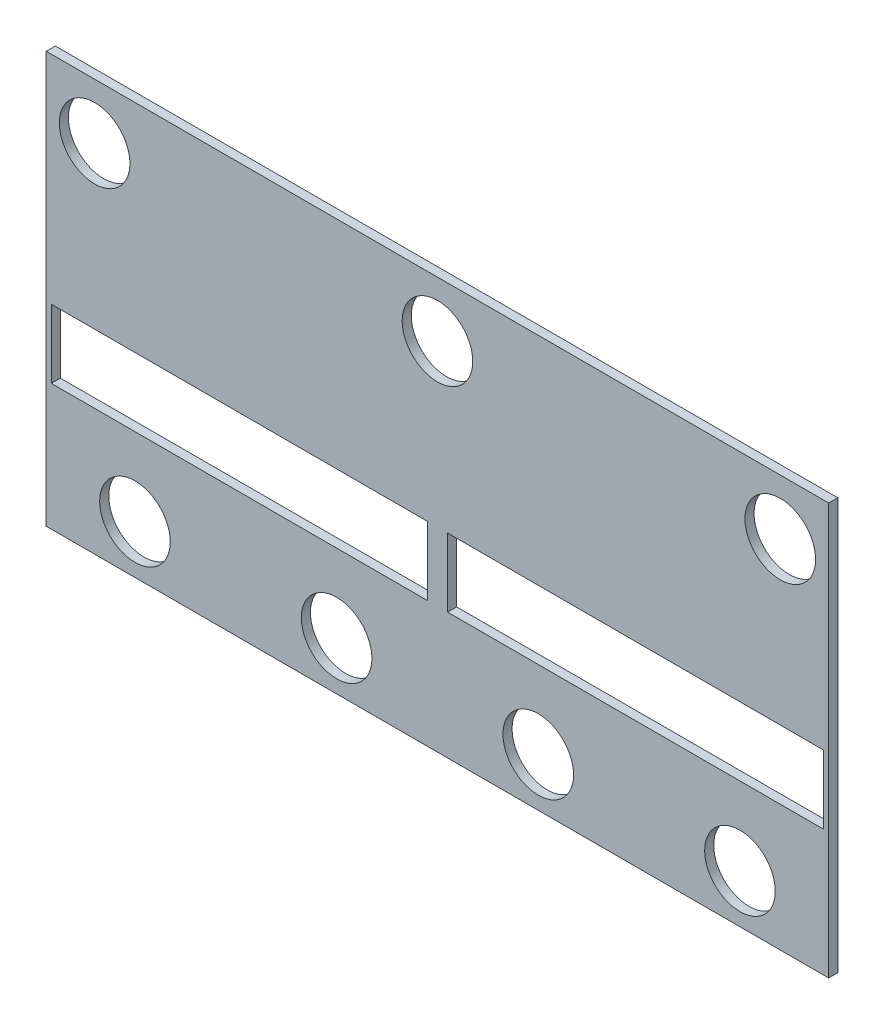
SolidWorks part; units mm, degrees
material "PLA"
ref_plane "Front" through (0, 0, 0) normal (0, 0, 1) x (1, 0, 0)
ref_plane "Top" through (0, 0, 0) normal (0, 1, 0) x (1, 0, 0)
ref_plane "Right" through (0, 0, 0) normal (1, 0, 0) x (0, 0, -1)
sketch "Sketch14" plane through (0, 0, 0) normal (0, 0, 1) x (1, 0, 0)
  line L0 (8.575, 1.875) -> (8.575, -1.875)
  line L1 (2.275, 1.875) -> (6.025, 1.875)
  line L2 (2.275, 1.875) -> (2.275, -1.875)
  line L3 (2.275, -1.875) -> (6.025, -1.875)
  line L4 (6.025, 1.875) -> (6.025, -1.875)
  line L5 (8.575, 1.875) -> (12.325, 1.875)
  line L6 (12.325, 1.875) -> (12.325, -1.875)
  line L7 (8.575, -1.875) -> (12.325, -1.875)
  line L8 (14.875, 1.875) -> (14.875, -1.875)
  line L9 (14.875, 1.875) -> (18.625, 1.875)
  line L10 (18.625, 1.875) -> (18.625, -1.875)
  line L11 (14.875, -1.875) -> (18.625, -1.875)
  line L12 (21.175, 1.875) -> (21.175, -1.875)
  line L13 (21.175, 1.875) -> (24.925, 1.875)
  line L14 (24.925, 1.875) -> (24.925, -1.875)
  line L15 (21.175, -1.875) -> (24.925, -1.875)
  line L16 (27.475, 1.875) -> (27.475, -1.875)
  line L17 (27.475, 1.875) -> (31.225, 1.875)
  line L18 (31.225, 1.875) -> (31.225, -1.875)
  line L19 (27.475, -1.875) -> (31.225, -1.875)
  line L20 (33.775, 1.875) -> (33.775, -1.875)
  line L21 (33.775, 1.875) -> (37.525, 1.875)
  line L22 (37.525, 1.875) -> (37.525, -1.875)
  line L23 (33.775, -1.875) -> (37.525, -1.875)
  line L24 (2.275, 1.875) -> (8.575, 1.875) construction
  line L25 (0, 1.875) -> (0, -1.875) construction
  line L26 (-33.775, -1.875) -> (-37.525, -1.875)
  line L27 (-37.525, 1.875) -> (-37.525, -1.875)
  line L28 (-33.775, 1.875) -> (-37.525, 1.875)
  line L29 (-33.775, 1.875) -> (-33.775, -1.875)
  line L30 (-27.475, -1.875) -> (-31.225, -1.875)
  line L31 (-31.225, 1.875) -> (-31.225, -1.875)
  line L32 (-27.475, 1.875) -> (-31.225, 1.875)
  line L33 (-27.475, 1.875) -> (-27.475, -1.875)
  line L34 (-21.175, -1.875) -> (-24.925, -1.875)
  line L35 (-24.925, 1.875) -> (-24.925, -1.875)
  line L36 (-21.175, 1.875) -> (-24.925, 1.875)
  line L37 (-21.175, 1.875) -> (-21.175, -1.875)
  line L38 (-14.875, -1.875) -> (-18.625, -1.875)
  line L39 (-18.625, 1.875) -> (-18.625, -1.875)
  line L40 (-14.875, 1.875) -> (-18.625, 1.875)
  line L41 (-14.875, 1.875) -> (-14.875, -1.875)
  line L42 (-8.575, -1.875) -> (-12.325, -1.875)
  line L43 (-12.325, 1.875) -> (-12.325, -1.875)
  line L44 (-8.575, 1.875) -> (-12.325, 1.875)
  line L45 (-6.025, 1.875) -> (-6.025, -1.875)
  line L46 (-2.275, -1.875) -> (-6.025, -1.875)
  line L47 (-2.275, 1.875) -> (-2.275, -1.875)
  line L48 (-2.275, 1.875) -> (-6.025, 1.875)
  line L49 (-8.575, 1.875) -> (-8.575, -1.875)
  line L51 (-40, 25) -> (40, 25)
  line L52 (-40, 25) -> (-40, -17)
  line L53 (-40, -17) -> (40, -17)
  line L54 (40, 25) -> (40, -17)
  line L55 (-40, 25) -> (40, -17) construction
  line L56 (-40, -17) -> (40, 25) construction
  point P0 (0, 4)
  point P53 (4.15, -1.875)
  point P54 (-4.15, -1.875)
  dimension "D1" = 3.75
  dimension "D2" = 6
  dimension "D3" = 6.3
  dimension "D4" = 8.3
  dimension "D5" = 17
  dimension "D6" = 25
  dimension "D7" = 80
extrude "BASE WITH CUTOUTS" add sketch "Sketch14" against normal blind 3
sketch "Sketch15" plane through (0, 0, -3) normal (0, 0, -1) x (-1, 0, 0)
  line L0 (-37.525, 1.875) -> (-33.775, 1.875) construction
  line L1 (-37.8, 2.525) -> (-33.5, 2.525)
  line L2 (-37.8, 2.525) -> (-37.8, -2.275)
  line L3 (-37.8, -2.275) -> (-33.5, -2.275)
  line L4 (-33.5, 2.525) -> (-33.5, -2.275)
  line L5 (-35.65, 2.525) -> (-35.65, 1.875) construction
  line L6 (0, 0) -> (0, -17) construction
  line L7 (40, -17) -> (-40, -17) construction
  line L8 (-31.5, 2.525) -> (-27.2, 2.525)
  line L9 (-31.5, 2.525) -> (-31.5, -2.275)
  line L10 (-31.5, -2.275) -> (-27.2, -2.275)
  line L11 (-27.2, 2.525) -> (-27.2, -2.275)
  line L12 (-29.35, 2.525) -> (-29.35, 1.875) construction
  line L13 (-25.2, 2.525) -> (-20.9, 2.525)
  line L14 (-25.2, 2.525) -> (-25.2, -2.275)
  line L15 (-25.2, -2.275) -> (-20.9, -2.275)
  line L16 (-20.9, 2.525) -> (-20.9, -2.275)
  line L17 (-23.05, 2.525) -> (-23.05, 1.875) construction
  line L18 (-18.9, 2.525) -> (-14.6, 2.525)
  line L19 (-18.9, 2.525) -> (-18.9, -2.275)
  line L20 (-18.9, -2.275) -> (-14.6, -2.275)
  line L21 (-14.6, 2.525) -> (-14.6, -2.275)
  line L22 (-16.75, 2.525) -> (-16.75, 1.875) construction
  line L23 (-12.6, 2.525) -> (-8.3, 2.525)
  line L24 (-12.6, 2.525) -> (-12.6, -2.275)
  line L25 (-12.6, -2.275) -> (-8.3, -2.275)
  line L26 (-8.3, 2.525) -> (-8.3, -2.275)
  line L27 (-10.45, 2.525) -> (-10.45, 1.875) construction
  line L28 (-6.3, 2.525) -> (-2, 2.525)
  line L29 (-6.3, 2.525) -> (-6.3, -2.275)
  line L30 (-6.3, -2.275) -> (-2, -2.275)
  line L31 (-2, 2.525) -> (-2, -2.275)
  line L32 (-4.15, 2.525) -> (-4.15, 1.875) construction
  line L33 (-6.025, 1.875) -> (-2.275, 1.875) construction
  line L34 (4.15, 2.525) -> (4.15, 1.875) construction
  line L35 (10.45, 2.525) -> (10.45, 1.875) construction
  line L36 (16.75, 2.525) -> (16.75, 1.875) construction
  line L37 (23.05, 2.525) -> (23.05, 1.875) construction
  line L38 (29.35, 2.525) -> (29.35, 1.875) construction
  line L39 (35.65, 2.525) -> (35.65, 1.875) construction
  line L40 (2, 2.525) -> (2, -2.275)
  line L41 (6.3, -2.275) -> (2, -2.275)
  line L42 (6.3, 2.525) -> (6.3, -2.275)
  line L43 (6.3, 2.525) -> (2, 2.525)
  line L44 (8.3, 2.525) -> (8.3, -2.275)
  line L45 (12.6, -2.275) -> (8.3, -2.275)
  line L46 (12.6, 2.525) -> (12.6, -2.275)
  line L47 (12.6, 2.525) -> (8.3, 2.525)
  line L48 (14.6, 2.525) -> (14.6, -2.275)
  line L49 (18.9, -2.275) -> (14.6, -2.275)
  line L50 (18.9, 2.525) -> (18.9, -2.275)
  line L51 (18.9, 2.525) -> (14.6, 2.525)
  line L52 (20.9, 2.525) -> (20.9, -2.275)
  line L53 (25.2, -2.275) -> (20.9, -2.275)
  line L54 (25.2, 2.525) -> (25.2, -2.275)
  line L55 (25.2, 2.525) -> (20.9, 2.525)
  line L56 (27.2, 2.525) -> (27.2, -2.275)
  line L57 (31.5, -2.275) -> (27.2, -2.275)
  line L58 (31.5, 2.525) -> (31.5, -2.275)
  line L59 (31.5, 2.525) -> (27.2, 2.525)
  line L60 (33.5, 2.525) -> (33.5, -2.275)
  line L61 (37.8, -2.275) -> (33.5, -2.275)
  line L62 (37.8, 2.525) -> (37.8, -2.275)
  line L63 (37.8, 2.525) -> (33.5, 2.525)
  line L64 (-33.775, -1.875) -> (-37.525, -1.875) construction
  dimension "D1" = 0.4
  dimension "D2" = 4.8
  dimension "D3" = 4.3
  dimension "D4" = 6
extrude "SIPM CUTOUTS" cut sketch "Sketch15" against normal through all
sketch "Sketch16" plane through (0, 0, 0) normal (0, 1, 0) x (1, 0, 0)
  line L0 (40, 0) -> (-40, 0) construction
  line L1 (40, 0) -> (37.6914, 0)
  line L2 (40, 0) -> (40, -16.79)
  line L4 (40, -16.79) -> (37.6914, 0)
  line L5 (0, 0) -> (2.3086, 0)
  line L6 (2.3086, 0) -> (0, -16.79)
  line L8 (0, -16.79) -> (0, 0) construction
  line L10 (-2.3086, 0) -> (0, -16.79)
  line L11 (0, 0) -> (-2.3086, 0)
  line L13 (-40, -16.79) -> (-37.6914, 0)
  line L15 (-40, 0) -> (-40, -16.79)
  line L16 (-40, 0) -> (-37.6914, 0)
  line L18 (37.275, 0) -> (40.025, -20) construction
  line L19 (37.275, 0) -> (37.275, -20) construction
  line L20 (37.275, -20) -> (40.025, -20) construction
  dimension "D1" = 2.3086
  dimension "D2" = 0.4125
  dimension "D3" = 20
  dimension "D4" = 2.75
extrude "PADDLE SUPPORT - TAPERS" add sketch "Sketch16" along normal mid plane 4
sketch "Sketch17" plane through (0, 2, 0) normal (0, 1, 0) x (1, 0, 0)
  line L1 (-40, 0) -> (40, 0)
  line L2 (-40, 0) -> (-40, -25)
  line L3 (-40, -25) -> (40, -25)
  line L4 (40, 0) -> (40, -25)
  dimension "D1" = 25
extrude "PADDLE SUPPORT - TOP" add sketch "Sketch17" along normal blind 1
extrude "PADDLE SUPPORT - BOTTOM" add sketch "Sketch17<2>" against normal blind 1 from surface starting at face at (0, -2, 3.358)
sketch "Sketch17<2>" plane through (0, 2, 0) normal (0, 1, 0) x (1, 0, 0) same geometry as "Sketch17"
chamfer "PADDLE SUPPORT - TAPER TOP" distance 0.8 distance2 2.4 1 edges at (0, 3, 25) first distance on face at (0, 2.5, 25)
chamfer "PADDLE SUPPORT - TAPER BOTTOM" distance 2.4 distance2 0.8 1 edges at (0, -3, 25) first distance on face at (0, -3, 12.5)
sketch "Sketch18" plane through (40, 0, 0) normal (1, 0, 0) x (0, 0, -1)
  line L0 (-22.6, 3) -> (0, 3) construction
  line L1 (0, 25) -> (-4, 25)
  line L2 (0, 25) -> (0, 3)
  line L3 (0, 3) -> (-4, 3)
  line L4 (-4, 25) -> (-4, 3)
  line L5 (-22.6, -3) -> (0, -3) construction
  line L6 (-4, -3) -> (0, -3)
  line L7 (-4, -3) -> (-4, -17)
  line L8 (-4, -17) -> (0, -17)
  line L9 (0, -3) -> (0, -17)
  line L10 (3, -17) -> (0, -17) construction
  line L11 (0, -17) -> (0, -3) construction
  dimension "D1" = 4
extrude "BASE - THICKNESS EXPANSION" add sketch "Sketch18" against normal up to surface (80 mm away) up to face at (-40, 1.1429, 12.3414)
ref_plane "ENCLOSURE MATE PLATE" through (0, 0, -3) normal (0, 0, -1) x (-1, 0, 0)
sketch "Sketch19" plane through (0, 0, -3) normal (0, 0, -1) x (-1, 0, 0)
  line L0 (-40, 16) -> (-39.2, 16)
  line L1 (-40, -17) -> (-40, 25) construction
  line L2 (-39.2, 16) -> (-39.2, -16.2)
  line L3 (-39.2, -16.2) -> (39.2, -16.2)
  line L4 (39.2, -16.2) -> (39.2, 16)
  line L5 (39.2, 16) -> (40, 16)
  line L6 (40, 25) -> (40, -17) construction
  line L7 (40, 16) -> (40, -17)
  line L8 (40, -17) -> (-40, -17)
  line L9 (-40, -17) -> (-40, 16)
  dimension "D1" = 0.8
  dimension "D2" = 33
  dimension "D3" = 0.8
extrude "BAFFLE - BASE" cut sketch "Sketch19" against normal blind 2
sketch "Sketch20" plane through (0, 0, -1) normal (0, 0, -1) x (-1, 0, 0)
  line L0 (-40, 16) -> (-40, -17)
  line L1 (-40, -17) -> (40, -17)
  line L2 (40, -17) -> (40, 16)
  line L3 (40, 16) -> (38.8, 16)
  line L4 (38.8, 16) -> (38.8, -15.8)
  line L5 (38.8, -15.8) -> (-38.8, -15.8)
  line L6 (-38.8, -15.8) -> (-38.8, 16)
  line L7 (-38.8, 16) -> (-40, 16)
  line L8 (-39.2, -16.2) -> (-39.2, 16) construction
  line L9 (39.2, -16.2) -> (-39.2, -16.2) construction
  dimension "D1" = 0.4
  dimension "D2" = 0.4
extrude "BAFFLE - LIP" cut sketch "Sketch20" against normal blind 2
chamfer "BAFFLE - CHAMFER 1.2" distance 1.2 angle 45 3 edges at (-40, -0.5, 1) (0, -17, 1) (40, -0.5, 1)
chamfer "BAFFLE - CHAMFER 0.4" distance 0.4 angle 45 3 edges at (39.2, -0.1, -1) (-39.2, -0.1, -1) (0, -16.2, -1)
hole_wizard "INSERT HOLES - PCB" positions "Sketch23" profile "Sketch25" legacy
sketch "Sketch23" plane through (0, 0, -3) normal (0, 0, -1) x (-1, 0, 0)
  line L0 (-30, -11) -> (-10, -11) construction
  line L1 (-34, 19.5) -> (0, 19.5) construction
  line L2 (0, 19.5) -> (0, 0) construction
  point P0 (-30, -11)
  point P5 (-10, -11)
  point P6 (10, -11)
  point P7 (30, -11)
  point P10 (-34, 19.5)
  point P15 (0, 19.5)
  point P16 (34, 19.5)
  dimension "D2" = 20
  dimension "D4" = 34
  dimension "D5" = 19.5
  dimension "D6" = 11
  dimension "D1" = 4
  dimension "D3" = 3
sketch "Sketch25" plane through (30, -11, -3) normal (1, 0, 0) x (0, 1, 0)
  line L0 (0, 0) -> (0, 4.2)
  line L1 (0, 4.2) -> (1.65, 4.2)
  line L2 (1.65, 4.2) -> (1.65, 1.4)
  line L3 (1.65, 1.4) -> (3.5, 1.4)
  line L4 (3.5, 1.4) -> (3.5, 0)
  line L5 (3.5, 0) -> (0, 0)
  line L6 (0, 110) -> (0, -10) construction
  dimension "Diameter" = 3.3
  dimension "Depth" = 4.2
  dimension "C-Bore Diameter" = 7
  dimension "C-Bore Depth" = 1.4
sketch "Sketch26" plane through (0, 0, -3) normal (0, 0, -1) x (-1, 0, 0)
  line L0 (-39.2, 16) -> (-40, 16) construction
  line L1 (-38.8, 16) -> (38.8, 16) construction
  line L2 (-38.8, 16) -> (-38.8, -15.8)
  line L3 (-38.8, -15.8) -> (38.8, -15.8)
  line L4 (38.8, 16) -> (38.8, -15.8)
  line L5 (-38.8, 16) -> (-39.2, 16)
  line L6 (39.2, 16) -> (38.8, 16)
  line L7 (38.8, 16) -> (38.8, -15.8) construction
  line L8 (-38.8, -15.8) -> (-38.8, 16) construction
  line L9 (38.8, -15.8) -> (-38.8, -15.8) construction
  line L18 (-40, 25) -> (-40, 16)
  line L19 (-40, 16) -> (-39.2, 16)
  line L20 (-39.2, 16) -> (-39.2, -16.2)
  line L21 (-39.2, -16.2) -> (39.2, -16.2)
  line L22 (39.2, -16.2) -> (39.2, 16)
  line L23 (39.2, 16) -> (40, 16)
  line L24 (40, 16) -> (40, 25)
  line L25 (40, 25) -> (-40, 25)
  line L28 (-39.2, 16) -> (-39.2, -16.2)
  line L29 (-39.2, -16.2) -> (39.2, -16.2)
  line L30 (39.2, -16.2) -> (39.2, 16)
  dimension "D1" = 0
extrude "JOINT MOD" cut sketch "Sketch26" against normal up to next
chamfer "PRINTING ASSIST 1" [suppressed] distance 0.25 distance2 0.5
chamfer "PRINTING ASSIST 2" [suppressed] distance 1 distance2 0.5
chamfer "PRINTING ASSIST 3" [suppressed] distance 1 distance2 1.2
sketch "Sketch29" plane through (0, 0, -3) normal (0, 0, -1) x (-1, 0, 0)
  line L0 (-2, -2.275) -> (-2, 2.525) construction
  line L1 (-38.3, 3.525) -> (-1, 3.525)
  line L2 (-38.3, 3.525) -> (-38.3, -3.275)
  line L3 (-38.3, -3.275) -> (-1, -3.275)
  line L4 (-1, 3.525) -> (-1, -3.275)
  line L5 (-2, 2.525) -> (-6.3, 2.525) construction
  line L6 (-6.3, -2.275) -> (-2, -2.275) construction
  line L7 (-37.8, 2.525) -> (-37.8, -2.275) construction
  line L8 (0, 0.77) -> (0, -0.77) construction
  line L9 (38.3, -3.275) -> (1, -3.275)
  line L10 (1, 3.525) -> (1, -3.275)
  line L11 (38.3, 3.525) -> (1, 3.525)
  line L12 (38.3, 3.525) -> (38.3, -3.275)
  point P6 (-1, 0.125)
  dimension "D1" = 1
  dimension "D2" = 1
  dimension "D3" = 1
  dimension "D4" = 0.5
extrude "Cut-Extrude1" cut sketch "Sketch29" against normal blind 1.45
chamfer "Chamfer1" distance 2 angle 70 1 edges at (0, 3, 4) first distance on face at (0, 3, 13.3)
sketch "Sketch34" plane through (0, 0, 25) normal (0, 0, 1) x (1, 0, 0)
  line L1 (-40.7498, 0.125) -> (40.7498, 0.125)
  line L2 (-40.7498, 0.125) -> (-40.7498, -0.125)
  line L3 (-40.7498, -0.125) -> (40.7498, -0.125)
  line L4 (40.7498, 0.125) -> (40.7498, -0.125)
  line L5 (-40.7498, 0.125) -> (40.7498, -0.125) construction
  line L6 (-40.7498, -0.125) -> (40.7498, 0.125) construction
  point P0 (0, 0)
  dimension "D1" = 0.25
extrude "Cut-Extrude2" cut sketch "Sketch34" against normal offset from surface (24 mm away) 1 up to face at (32.5, 0, 0)
hole_wizard "M1.6 Clearance Hole1" positions "Sketch35" profile "Sketch36" hole size "M1.6" standard "ANSI Metric" end condition through all
sketch "Sketch35" plane through (0, -3, 0) normal (0, -1, 0) x (-1, 0, 0)
  point P0 (0, -8)
  dimension "D1" = 8
sketch "Sketch36" plane through (0, -3, 8) normal (1, 0, 0) x (0, 0, -1)
  line L0 (0, 0) -> (0, 28)
  line L1 (0, 28) -> (0.9, 28)
  line L2 (0.9, 28) -> (0.9, 0)
  line L5 (0.9, 0) -> (0, 0)
  line L11 (0, -6.35) -> (0, 107.95) construction
  dimension "Thru Hole Dia." = 1.8
  dimension "Thru Hole Depth" = 28
sketch "Sketch38" plane through (0, 0, -1.55) normal (0, 0, -1) x (-1, 0, 0)
  line L1 (-52.0502, 27.4011) -> (52.0502, 27.4011)
  line L2 (-52.0502, 27.4011) -> (-52.0502, -27.4011)
  line L3 (-52.0502, -27.4011) -> (52.0502, -27.4011)
  line L4 (52.0502, 27.4011) -> (52.0502, -27.4011)
  line L5 (-52.0502, 27.4011) -> (52.0502, -27.4011) construction
  line L6 (-52.0502, -27.4011) -> (52.0502, 27.4011) construction
  point P0 (0, 0)
extrude "Cut-Extrude3" cut sketch "Sketch38" against normal through all
sketch "Sketch39" plane through (0, 0, -1.55) normal (0, 0, 1) x (1, 0, 0)
  line L16 (40, 25) -> (-40, 25)
  line L17 (-40, 25) -> (-40, 16)
  line L18 (-40, 16) -> (-38.8, 16)
  line L19 (-38.8, 16) -> (-38.8, -15.8)
  line L20 (-38.8, -15.8) -> (38.8, -15.8)
  line L21 (38.8, -15.8) -> (38.8, 16)
  line L22 (38.8, 16) -> (40, 16)
  line L23 (40, 16) -> (40, 25)
  line L24 (40, 25) -> (-40, 25)
  line L25 (-40, 25) -> (-40, 16)
  line L26 (-40, 16) -> (-38.8, 16)
  line L27 (-38.8, 16) -> (-38.8, -15.8)
  line L28 (-38.8, -15.8) -> (38.8, -15.8)
  line L29 (38.8, -15.8) -> (38.8, 16)
  line L30 (38.8, 16) -> (40, 16)
  line L31 (40, 16) -> (40, 25)
  dimension "D1" = 0
extrude "Cut-Extrude4" cut sketch "Sketch39" against normal up to surface (0.05 mm away) up to face at (-11.65, -11, -1.6)
sketch "Sketch40" plane through (0, 0, -1.6) normal (0, 0, 1) x (1, 0, 0)
  line L1 (-40, 25) -> (-38.8, 25)
  line L2 (-40, 25) -> (-40, 16)
  line L3 (-40, 16) -> (-38.8, 16)
  line L4 (-38.8, 25) -> (-38.8, 16)
  line L5 (40, 25) -> (38.8, 25)
  line L6 (40, 25) -> (40, 16)
  line L7 (40, 16) -> (38.8, 16)
  line L8 (38.8, 25) -> (38.8, 16)
extrude "Cut-Extrude5" cut sketch "Sketch40" against normal through all
sketch "Sketch41" plane through (0, 0, -1.6) normal (0, 0, 1) x (1, 0, 0)
  line L1 (-38.8, 25) -> (38.8, 25)
  line L2 (-38.8, 25) -> (-38.8, -15.8)
  line L3 (-38.8, -15.8) -> (38.8, -15.8)
  line L4 (38.8, 25) -> (38.8, -15.8)
extrude "Cut-Extrude6" cut sketch "Sketch41" against normal offset from surface (0.5 mm away) 0.9 up to face at (19.65, 0.125, -3)
